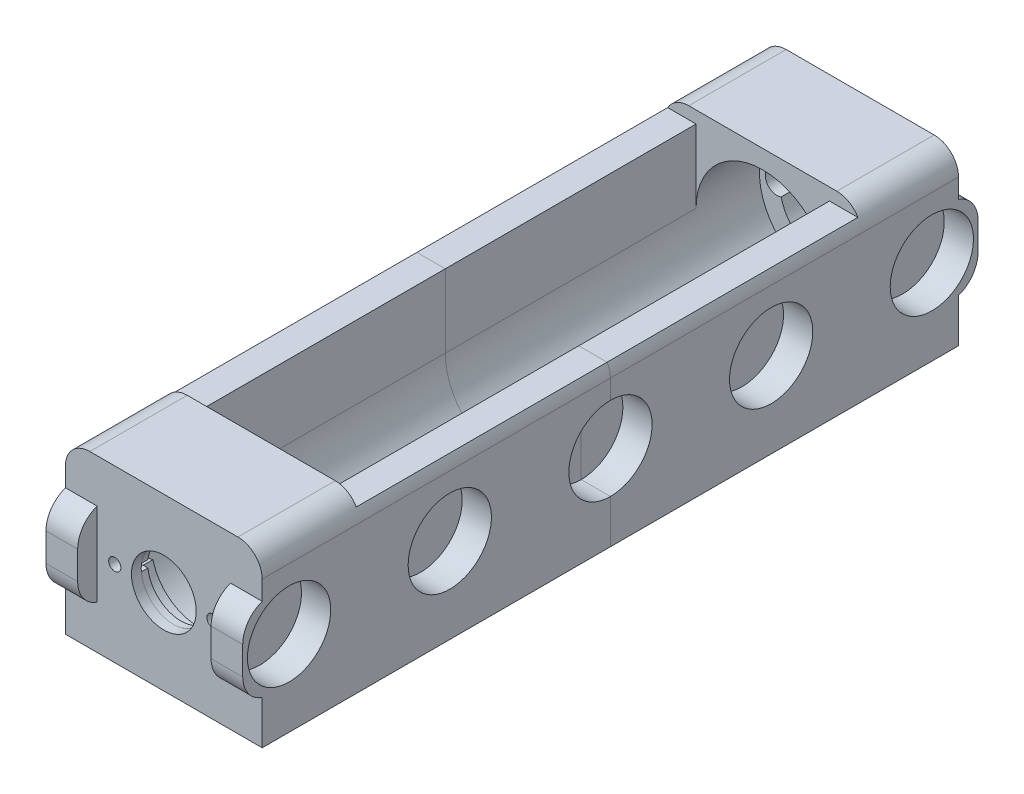
SolidWorks part; units mm, degrees
ref_plane "Alzado" through (0, 0, 0) normal (0, 0, 1) x (1, 0, 0)
ref_plane "Planta" through (0, 0, 0) normal (0, 1, 0) x (1, 0, 0)
ref_plane "Vista lateral" through (0, 0, 0) normal (1, 0, 0) x (0, 0, -1)
sketch "Croquis1" plane through (0, 0, 0) normal (0, 0, 1) x (1, 0, 0)
  line L0 (0, 8.3596) -> (0, -1.3417) construction
  line L1 (9, 0.75) -> (-9, 0.75)
  line L2 (0, 0.75) -> (0, -0.75)
  line L3 (9, -0.75) -> (-9, -0.75)
  line L4 (-9, 0.75) -> (-9, -0.75)
  line L5 (-12.48, 10.7299) -> (-12.48, -4.9079) construction
  line L6 (9, 0.75) -> (9, -0.75)
  line L7 (0, 0) -> (-17.6562, 0) construction
  circle A0 centre (-10.08, 0) radius 2.4
  circle A1 centre (-10.08, 0) radius 0.9
  circle A2 centre (10.08, 0) radius 0.9
  circle A3 centre (10.08, 0) radius 2.4
  circle A4 centre (0, 0) radius 13.7
  point P9 (0, 0)
  dimension "D1" = 1.8
  dimension "D4" = 4.8
  dimension "D6" = 27.4
  dimension "D2" = 1.5
  dimension "D3" = 9
  dimension "D5" = 12.48
extrude "Saliente-Extruir1" add sketch "Croquis1" along normal blind 5 contours A4 L1 A3 L3 A0 region at (-13.3125, 0, 0)
sketch "Croquis2" plane through (0, 0, 5) normal (0, 0, 1) x (1, 0, 0)
  circle A0 centre (0, 0) radius 9.5
  dimension "D1" = 19
extrude "Cortar-Extruir1" cut sketch "Croquis2" against normal blind 3.5
sketch "Croquis3" plane through (0, 0, 1.5) normal (0, 0, 1) x (1, 0, 0)
  circle A0 centre (0, 0) radius 6.8
  dimension "D1" = 13.6
extrude "Cortar-Extruir2" cut sketch "Croquis3" against normal blind 3
sketch "Croquis4" plane through (0, 0, 0) normal (0, 0, -1) x (-1, 0, 0)
  circle A0 centre (0, 0) radius 13.7 construction
  circle A1 centre (0, 0) radius 13.7
  circle A2 centre (0, 0) radius 6.65
  dimension "D1" = 13.3
extrude "Saliente-Extruir2" add sketch "Croquis4" along normal blind 2
sketch "Croquis5" plane through (0, 0, 5) normal (0, 0, 1) x (1, 0, 0)
  circle A0 centre (-10.08, 0) radius 1.25
  circle A1 centre (10.08, 0) radius 1.25
  dimension "D1" = 2.5
  dimension "D2" = 2.5
extrude "Cortar-Extruir3" cut sketch "Croquis5" against normal through all
sketch "Croquis6" plane through (0, 0, -2) normal (0, 0, -1) x (-1, 0, 0)
  line L1 (-20.2, -17.5) -> (20.2, -17.5)
  line L2 (-20.2, -17.5) -> (-20.2, 17.5)
  line L3 (-20.2, 17.5) -> (20.2, 17.5)
  line L4 (20.2, -17.5) -> (20.2, 17.5)
  line L5 (-20.2, -17.5) -> (20.2, 17.5) construction
  line L6 (-20.2, 17.5) -> (20.2, -17.5) construction
  circle A0 centre (0, 0) radius 13.7 construction
  circle A1 centre (0, 0) radius 13.7
  point P0 (0, 0)
  dimension "D1" = 35
  dimension "D2" = 40.4
extrude "Saliente-Extruir3" add sketch "Croquis6" against normal blind 20 separate body
sketch "Croquis8" plane through (0, 0, 18) normal (0, 0, 1) x (1, 0, 0)
  line L0 (-13.7, 0) -> (-13.7, 15)
  line L1 (-13.7, 15) -> (20.2, 15)
  line L2 (13.7, 0) -> (13.7, 15)
  line L3 (13.7, 15) -> (-20.2, 15)
  line L4 (-20.2, 17.5) -> (-20.2, -17.5)
  line L5 (20.2, 17.5) -> (-20.2, 17.5)
  line L6 (20.2, -17.5) -> (20.2, 17.5)
  line L7 (-20.2, -17.5) -> (20.2, -17.5)
  line L8 (-20.2, 17.5) -> (-20.2, 15)
  line L10 (20.2, 15) -> (20.2, 17.5)
  line L11 (-20.2, -17.5) -> (20.2, -17.5)
  line L12 (20.2, 17.5) -> (20.2, -17.5) construction
  line L13 (27.021, 0) -> (-27.7174, 0) construction
  circle A0 centre (0, 0) radius 13.7 construction
  circle A1 centre (0, 0) radius 13.7 construction
  arc A2 (-13.7, 0) -> (13.7, 0) centre (0, 0) ccw
  circle M15 centre (0, 0) radius 13.7
  line M16 (-20.2, 17.5) -> (-20.2, -17.5)
  line M17 (-20.2, -17.5) -> (20.2, -17.5)
  line M18 (20.2, -17.5) -> (20.2, 17.5)
  dimension "D2" = 15
  dimension "D3" = 15
  dimension "D1" = 0
extrude "Saliente-Extruir5" add sketch "Croquis8" along normal blind 51.5 contours L13 M18 M15 M16 M17 | L13 L0 L3 M16 | L13 L1 L2 M18 region at (-16.95, 7.5, 18) region at (0, -14.1403, 18) region at (16.95, 7.5, 18)
sketch "Croquis11" plane through (0, 0, -2) normal (0, 0, -1) x (-1, 0, 0)
  line L0 (25.6797, 0) -> (-27.0718, 0) construction
  line L1 (-20.2, 8.55) -> (-13.7, 8.55)
  line L2 (-20.2, 8.55) -> (-20.2, -8.55)
  line L3 (-20.2, -8.55) -> (-13.7, -8.55)
  line L4 (-13.7, 8.55) -> (-13.7, -8.55)
  line L5 (0, 15.867) -> (0, -22.027) construction
  line L6 (20.2, -8.55) -> (13.7, -8.55)
  line L7 (13.7, 8.55) -> (13.7, -8.55)
  line L8 (20.2, 8.55) -> (13.7, 8.55)
  line L9 (20.2, 8.55) -> (20.2, -8.55)
  circle A0 centre (0, 0) radius 13.7 construction
  dimension "D1" = 17.1
  dimension "D2" = 6.5
extrude "Saliente-Extruir6" add sketch "Croquis11" along normal blind 4
ref_plane "Plano1" through (0, 0, 69.5) normal (0, 0, 1) x (1, 0, 0)
mirror "Simetría10" about plane through (0, 0, 69.5) normal (0, 0, 1) of bodies 126 105 108
sketch "Croquis9" plane through (-20.2, 0, 0) normal (-1, 0, 0) x (0, 0, 1)
  line L0 (0, 0) -> (156.1517, 0) construction
  circle A0 centre (3.4791, 0) radius 8.55
  circle A1 centre (3.4791, 0) radius 16.5 construction
  circle A2 centre (36.4791, 0) radius 16.5 construction
  circle A3 centre (69.4791, 0) radius 16.5 construction
  circle A4 centre (102.4791, 0) radius 16.5 construction
  circle A5 centre (135.4791, 0) radius 16.5 construction
  circle A6 centre (36.4791, 0) radius 8.55
  circle A7 centre (69.4791, 0) radius 8.55
  circle A8 centre (102.4791, 0) radius 8.55
  circle A9 centre (135.4791, 0) radius 8.55
  dimension "D1" = 17.1
  dimension "D3" = 33
  dimension "D2" = 3.4791
extrude "Cortar-Extruir4" cut sketch "Croquis9" against normal blind 6
mirror "Simetría11" about plane through (0, 0, 0) normal (1, 0, 0) of "Cortar-Extruir4"
fillet "Redondeo1" radius 5 2 edges at (20.2, 17.5, 8) (-20.2, 17.5, 8)
fillet "Redondeo2" radius 5 2 edges at (20.2, 17.5, 131) (-20.2, 17.5, 131)
ref_plane "Plano2" [suppressed] through (0, -13.7, 0) normal (0, 1, 0) x (1, 0, 0)
sketch "Croquis10" plane through (0, 0, 0) normal (0, -1, 0) x (1, 0, 0)
  line L0 (0, -25.2789) -> (0, 143.4615) construction
  circle A0 centre (0, 50) radius 4
  circle A1 centre (0, 113) radius 4
  circle A2 centre (0, 88) radius 4
  circle A3 centre (0, 25) radius 4
  dimension "D1" = 8
  dimension "D2" = 25
  dimension "D3" = 25
  dimension "D4" = 38
  dimension "D5" = 25
extrude "Cortar-Extruir5" cut sketch "Croquis10" along normal blind 16
sketch "Croquis12" plane through (0, 0, 0) normal (0, -1, 0) x (1, 0, 0)
  line L0 (0, -25.2789) -> (0, 143.4615) construction
  circle A0 centre (0, 50) radius 2
  circle A1 centre (0, 113) radius 2
  circle A2 centre (0, 88) radius 2
  circle A3 centre (0, 25) radius 2
  dimension "D1" = 4
  dimension "D2" = 25
  dimension "D3" = 25
  dimension "D4" = 38
  dimension "D5" = 25
extrude "Cortar-Extruir6" cut sketch "Croquis12" along normal blind 24
fillet "Redondeo4" radius 6 4 edges at (-16.95, -8.55, 145) (-16.95, 8.55, 145) (16.95, -8.55, 145) (16.95, 8.55, 145)
fillet "Redondeo5" radius 6 4 edges at (-16.95, -8.55, -6) (-16.95, 8.55, -6) (16.95, -8.55, -6) (16.95, 8.55, -6)
